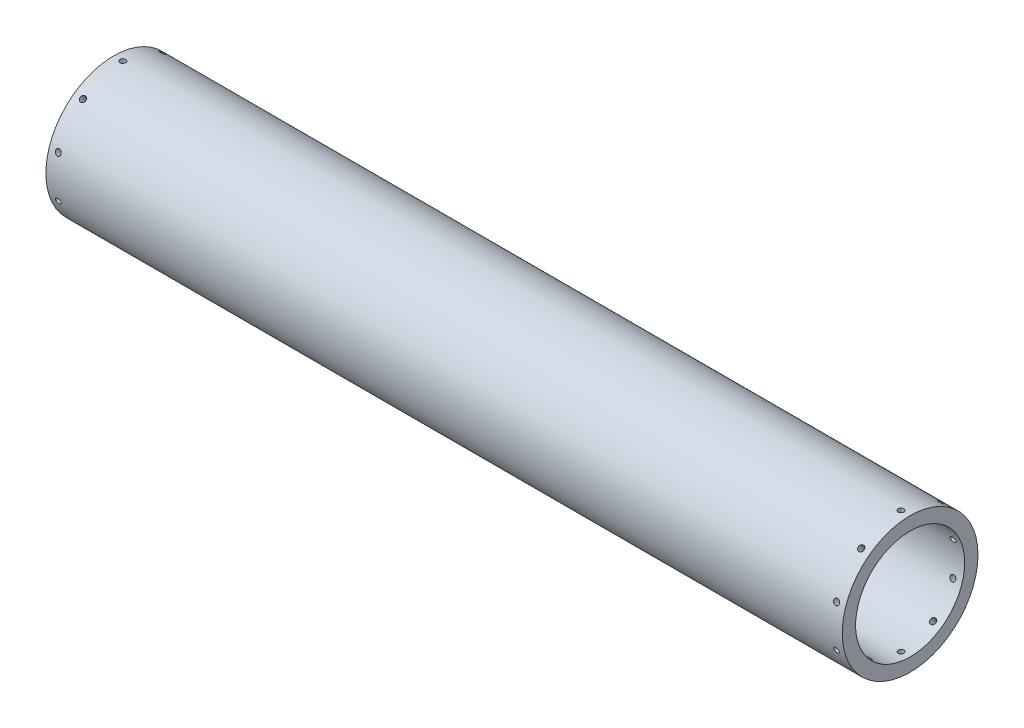
SolidWorks part; units mm, degrees
material "7075-T6 (SN)"
ref_plane "Front Plane" through (0, 0, 0) normal (0, 0, 1) x (1, 0, 0)
ref_plane "Top Plane" through (0, 0, 0) normal (0, 1, 0) x (1, 0, 0)
ref_plane "Right Plane" through (0, 0, 0) normal (1, 0, 0) x (0, 0, -1)
sketch "Sketch1" plane through (0, 0, 0) normal (1, 0, 0) x (0, 0, -1)
  circle A0 centre (0, 0) radius 45.9486
  circle A1 centre (0, 0) radius 57.15
  dimension "D1" = 91.8972
  dimension "D2" = 114.3
extrude "Boss-Extrude1" add sketch "Sketch1" along normal blind 670.56
sketch "Sketch4" plane through (0, 0, 0) normal (0, 0, 1) x (1, 0, 0)
  line L0 (0, 0) -> (0, 88.0135) construction
  line L1 (0, 57.15) -> (0, -57.15) construction
  line L2 (0, -55) -> (0, 55) construction
  line L3 (0, 0) -> (-48.5735, 0) construction
ref_plane "Plane1" through (0, 57.15, 0) normal (0, 1, 0) x (1, 0, 0)
sketch "Sketch6" plane through (0, 57.15, 0) normal (0, 1, 0) x (1, 0, 0)
  line L0 (0, 57.15) -> (0, -57.15) construction
  circle A0 centre (7.62, 0) radius 2.413
  dimension "D1" = 4.826
  dimension "D2" = 7.62
extrude "Cut-Extrude1" cut sketch "Sketch6" against normal blind 15.24
sketch "Sketch7" plane through (0, 57.15, 0) normal (0, 1, 0) x (1, 0, 0)
  line L0 (670.56, -57.15) -> (670.56, 57.15) construction
  circle A0 centre (662.94, 0) radius 2.413
  dimension "D2" = 4.826
  dimension "D1" = 7.62
extrude "Cut-Extrude2" cut sketch "Sketch7" against normal blind 15.24
pattern_circular "CirPattern2" count 10 every 36 about axis through (670.56, 0, 0) along (1, 0, 0) of "Cut-Extrude2"
pattern_circular "CirPattern3" count 10 every 36 about axis through (0, 0, 0) along (-1, 0, 0) of "Cut-Extrude1"
